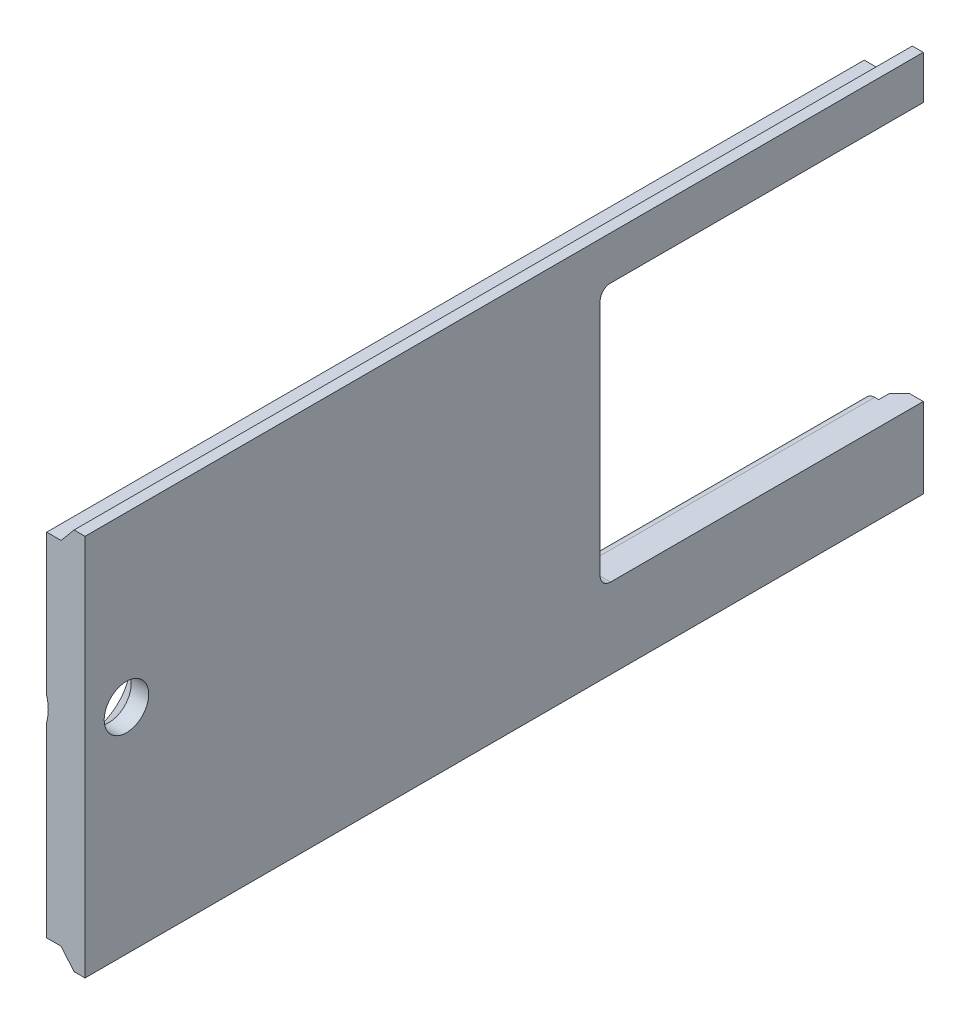
SolidWorks part; units mm, degrees
ref_plane "Plan de face" through (0, 0, 0) normal (0, 0, 1) x (1, 0, 0)
ref_plane "Plan de dessus" through (0, 0, 0) normal (0, 1, 0) x (1, 0, 0)
ref_plane "Plan de droite" through (0, 0, 0) normal (1, 0, 0) x (0, 0, -1)
sketch "Esquisse1" plane through (0, 0, 0) normal (0, 0, 1) x (1, 0, 0)
  line L0 (-17.6384, 37.24) -> (-16.2479, 37.24)
  line L1 (-17.6384, 37.24) -> (-17.6384, 3.3)
  line L3 (-17.6384, 3.3) -> (-16.2479, 3.3)
  line L5 (-14.9979, 38.74) -> (-13.9384, 38.74)
  line L7 (-13.9384, 38.74) -> (-13.9384, 1.8)
  line L8 (-13.9384, 1.8) -> (-14.9979, 1.8)
  line L10 (-16.3884, 37.54) -> (-17.6384, 37.54) construction
  line L11 (-16.3884, 3) -> (-17.6384, 3) construction
  line L16 (-13.6384, 38.54) -> (-13.6384, 2) construction
  line L17 (-17.6384, 38.54) -> (-17.6384, 37.54) construction
  line L18 (-14.9979, 38.74) -> (-16.2479, 37.24)
  line L19 (-16.2479, 3.3) -> (-14.9979, 1.8)
  line L20 (-15.5551, 2) -> (-16.3884, 3) construction
  line L21 (-13.6384, 1.5) -> (-15.1384, 1.5) construction
  line L22 (-15.5551, 38.54) -> (-16.3884, 37.54) construction
  line L23 (-13.6384, 39.04) -> (-15.1384, 39.04) construction
  point P16 (-17.0134, 3)
  dimension "D1" = 0.3
  dimension "D2" = 0.3
  dimension "D3" = 0.3
  dimension "D4" = 0.3
  dimension "D5" = 0.3
  dimension "D6" = 0.3
  dimension "D7" = 0.3
extrude "Boss.-Extru.1" add sketch "Esquisse1" against normal offset from surface (78.95 mm away) 0.3
sketch "Esquisse2" plane through (0, 0, -78.95) normal (0, 0, -1) x (-1, 0, 0)
  line L0 (16.2479, 37.24) -> (16.2479, 3.3)
  line L8 (14.9979, 1.8) -> (16.2479, 3.3)
  line L9 (16.2479, 3.3) -> (17.6384, 3.3)
  line L10 (17.6384, 3.3) -> (17.6384, 37.24)
  line L11 (17.6384, 37.24) -> (16.2479, 37.24)
  line L12 (16.2479, 37.24) -> (14.9979, 38.74)
  line L13 (14.9979, 38.74) -> (13.9384, 38.74)
  line L14 (13.9384, 38.74) -> (13.9384, 1.8)
  line L15 (13.9384, 1.8) -> (14.9979, 1.8)
  line L16 (14.9979, 1.8) -> (16.2479, 3.3)
  line L20 (16.2479, 37.24) -> (14.9979, 38.74)
  line L21 (14.9979, 38.74) -> (13.9384, 38.74)
  line L22 (13.9384, 38.74) -> (13.9384, 1.8)
  line L23 (13.9384, 1.8) -> (14.9979, 1.8)
  dimension "D1" = 0
extrude "Boss.-Extru.2" add sketch "Esquisse2" along normal blind 2
chamfer "Chanfrein1" distance 1 angle 45 1 edges at (-16.2479, 20.27, -80.95)
sketch "Esquisse3" plane through (-17.6384, 0, 0) normal (-1, 0, 0) x (0, 0, 1)
  circle A0 centre (-4, 22.4617) radius 2.15
  dimension "D1" = 4.3
extrude "Enlèv. mat.-Extru.1" cut sketch "Esquisse3" against normal up to next
chamfer "Chanfrein2" distance 2 angle 45 1 edges at (-17.6384, 20.3117, -4)
sketch "Esquisse4" plane through (-17.6384, 0, 0) normal (-1, 0, 0) x (0, 0, 1)
  line L0 (-83, 34.54) -> (-49.7481, 34.54)
  line L3 (-83, 34.54) -> (-83, 9.54)
  line L4 (-49.7481, 34.54) -> (-49.7481, 9.54)
  line L5 (-83, 9.54) -> (-49.7481, 9.54)
  line L6 (-49.7481, 32.54) -> (-49.7481, 14.54) construction
  line L7 (-4.75, 9.54) -> (-77.95, 9.54) construction
  line L8 (-83, 38.54) -> (-83, 2) construction
  dimension "D1" = 0
  dimension "D2" = 0
  dimension "D3" = 25
extrude "Enlèv. mat.-Extru.2" cut sketch "Esquisse4" against normal through all
fillet "Congé2" radius 1 2 edges at (-17.6384, 34.54, -64.3491) (-17.6384, 9.54, -64.3491)
fillet "Congé1" radius 1 4 edges at (-15.2884, 9.54, -49.7481) (-15.2884, 34.54, -49.7481) (-17.3455, 9.2471, -49.7481) (-17.3455, 34.8329, -49.7481)
sketch "Esquisse5" plane through (-17.6384, 0, 0) normal (-1, 0, 0) x (0, 0, 1)
  line L0 (-18.638, 22.4617) -> (-40.7286, 22.4617) construction
  line L1 (-18.638, 17.8279) -> (-40.7286, 17.8279)
  line L2 (-18.638, 27.0955) -> (-40.7286, 27.0955)
  arc A0 (-18.638, 17.8279) -> (-18.638, 27.0955) centre (-18.638, 22.4617) ccw
  arc A1 (-40.7286, 27.0955) -> (-40.7286, 17.8279) centre (-40.7286, 22.4617) ccw
  point P3 (-29.6833, 22.4617)
extrude "Enlèv. mat.-Extru.3" cut sketch "Esquisse5" against normal blind 2
fillet "Congé3" radius 1 4 edges at (-15.6384, 27.0955, -29.6833) (-15.6384, 22.4617, -14.0042) (-15.6384, 17.8279, -29.6833) (-15.6384, 22.4617, -45.3624)
fillet "Congé4" radius 1 1 edges at (-17.6384, 22.4617, -14.0042)
